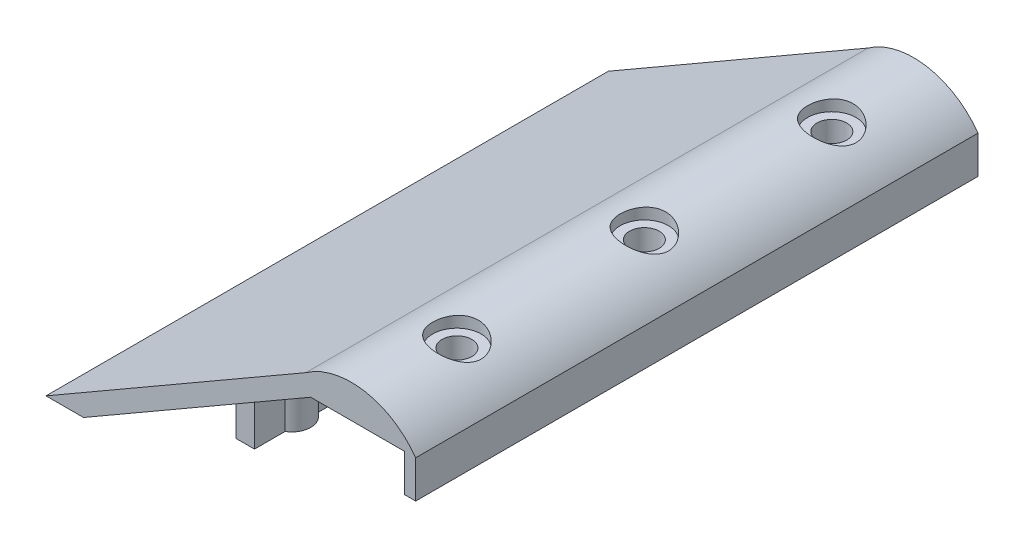
SolidWorks part; units mm, degrees
ref_plane "Alzado" through (0, 0, 0) normal (0, 0, 1) x (1, 0, 0)
ref_plane "Planta" through (0, 0, 0) normal (0, 1, 0) x (1, 0, 0)
ref_plane "Vista lateral" through (0, 0, 0) normal (1, 0, 0) x (0, 0, -1)
sketch "Croquis1" plane through (0, 0, 0) normal (0, 0, 1) x (1, 0, 0)
  line L0 (0, 34.3848) -> (0, -4.3701) construction
  line L1 (-35.1904, 0) -> (25, 0) construction
  line L2 (0, 0) -> (25, 0)
  line L3 (25, 0) -> (25, 5) construction
  line L4 (25, 5) -> (-1.3397, 5) construction
  line L5 (-1.3397, 5) -> (-70.6218, -35)
  line L6 (-70.6218, -35) -> (-60.6218, -35)
  line L7 (-60.6218, -35) -> (0, 0)
  line L8 (-73.772, -35) -> (41.2109, -35) construction
  line L9 (34.3149, -26) -> (-26.4016, -26) construction
  line L10 (-77.6138, -56) -> (49.339, -56) construction
  line L11 (0, 0) -> (25, 0) construction
  line L12 (0, 0) -> (25, 0)
  line L13 (0, 0) -> (25, 0)
  line L14 (25, 0) -> (25, -10)
  line L15 (25, -10) -> (28, -10)
  line L16 (28, -10) -> (28, 0)
  line L17 (-4.6669, 0) -> (44.3879, 0) construction
  arc A0 (-1.3397, 5) -> (28, 0) centre (10.8301, -12.1699) cw
  dimension "D8" = 10
  dimension "D10" = 21.0454
  dimension "D1" = 25
  dimension "D2" = 30
  dimension "D3" = 5
  dimension "D4" = 5
  dimension "D5" = 26
  dimension "D6" = 30
  dimension "D7" = 35
  dimension "D9" = 3
extrude "Saliente-Extruir1" add sketch "Croquis1" along normal mid plane 150 contours A0 L5 L6 L7 L2 L14 L15 L16 region at (-30.8506, -16.5652, 0)
ref_plane "Plano Tangente Para Perforacion" through (0, 8.8756, 0) normal (0, 1, 0) x (1, 0, 0)
ref_plane "Bases Soporte" through (0, -15, 0) normal (0, 1, 0) x (1, 0, 0)
sketch "Croquis2" plane through (0, -15, 0) normal (0, 1, 0) x (1, 0, 0)
  line L0 (122.6306, 0) -> (-182.6306, 0) construction
  line L1 (0, 52.1261) -> (0, -47.2849) construction
  line L2 (-30, 99.6856) -> (-30, -100.7612) construction
  line L3 (-32.5, 4.3301) -> (-32.5, 12.5)
  line L4 (-32.5, -12.5) -> (-27.5, -12.5)
  line L5 (-32.5, -12.5) -> (-32.5, -4.3301)
  line L6 (-32.5, 12.5) -> (-27.5, 12.5)
  line L7 (-27.5, -12.5) -> (-27.5, -4.3301)
  line L8 (-32.5, -12.5) -> (-27.5, 12.5) construction
  line L9 (-32.5, 12.5) -> (-27.5, -12.5) construction
  line L10 (-27.5, 4.3301) -> (-27.5, 12.5)
  line L17 (-32.5, 54.3301) -> (-32.5, 62.5)
  line L24 (-32.5, 37.5) -> (-27.5, 37.5)
  line L25 (-32.5, 37.5) -> (-32.5, 45.6699)
  line L26 (-32.5, 62.5) -> (-27.5, 62.5)
  line L27 (-27.5, 37.5) -> (-27.5, 45.6699)
  line L28 (-27.5, 54.3301) -> (-27.5, 62.5)
  line L29 (-32.5, 37.5) -> (-27.5, 62.5) construction
  line L30 (-32.5, 62.5) -> (-27.5, 37.5) construction
  line L31 (-32.5, 4.3301) -> (-32.5, 54.3301) construction
  line L32 (-32.5, -45.6699) -> (-32.5, -37.5)
  line L33 (-32.5, -62.5) -> (-27.5, -62.5)
  line L34 (-32.5, -62.5) -> (-32.5, -54.3301)
  line L35 (-32.5, -37.5) -> (-27.5, -37.5)
  line L36 (-27.5, -62.5) -> (-27.5, -54.3301)
  line L37 (-27.5, -45.6699) -> (-27.5, -37.5)
  line L38 (-32.5, -62.5) -> (-27.5, -37.5) construction
  line L39 (-32.5, -37.5) -> (-27.5, -62.5) construction
  line L40 (-32.5, 4.3301) -> (-32.5, -45.6699) construction
  arc A0 (-32.5, 4.3301) -> (-32.5, -4.3301) centre (-30, 0) ccw
  arc A2 (-27.5, -4.3301) -> (-27.5, 4.3301) centre (-30, 0) ccw
  arc A6 (-32.5, 54.3301) -> (-32.5, 45.6699) centre (-30, 50) ccw
  arc A7 (-27.5, 45.6699) -> (-27.5, 54.3301) centre (-30, 50) ccw
  arc A8 (-32.5, -45.6699) -> (-32.5, -54.3301) centre (-30, -50) ccw
  arc A9 (-27.5, -54.3301) -> (-27.5, -45.6699) centre (-30, -50) ccw
  dimension "D1" = 10
  dimension "D2" = 30
  dimension "D3" = 5
  dimension "D4" = 25
  dimension "D5" = 2
  dimension "D6" = 50
  dimension "D8" = 50
  dimension "D7" = 2
extrude "Saliente-Extruir2" add sketch "Croquis2" against normal blind 17
sketch "Croquis3" plane through (0, 8.8756, 0) normal (0, 1, 0) x (1, 0, 0)
  line L0 (0, -113.8566) -> (0, 103.3108) construction
  line L1 (55.4509, 0) -> (-87.9325, 0) construction
  line L2 (14, 0) -> (14, 50) construction
  line L3 (14, 0) -> (14, -50) construction
  line L6 (28, 75) -> (-1.3397, 75)
  line L7 (-1.3397, 75) -> (-1.3397, -75)
  line L8 (-1.3397, -75) -> (28, -75)
  line L9 (28, -75) -> (28, 75)
  line L10 (28, 75) -> (-1.3397, 75)
  line L11 (-1.3397, 75) -> (-1.3397, -75)
  line L12 (-1.3397, -75) -> (28, -75)
  line L13 (28, -75) -> (28, 75)
  circle A0 centre (14, 0) radius 3.9687
  circle A1 centre (14, 50) radius 3.9688
  circle A2 centre (14, -50) radius 3.9687
  dimension "D3" = 7.9375
  dimension "D2" = 14
  dimension "D5" = 50
  dimension "D7" = 50
  dimension "D1" = 0
  dimension "D4" = 2
  dimension "D6" = 2
extrude "Cortar-Extruir1" cut sketch "Croquis3" against normal blind 10 contours A2 | A0 | A1 region at (14, 8.8756, 0) region at (14, 8.8756, -50) region at (14, 8.8756, 50)
sketch "Croquis4" plane through (0, 8.8756, 0) normal (0, 1, 0) x (1, 0, 0)
  circle A0 centre (14, 50) radius 3.9688 construction
  circle A1 centre (14, -50) radius 3.9688 construction
  circle A2 centre (14, 0) radius 3.9687 construction
  circle A3 centre (14, 50) radius 3.9688
  circle A4 centre (14, -50) radius 3.9688
  circle A5 centre (14, 0) radius 3.9687
  circle A6 centre (14, 50) radius 6.4688
  circle A7 centre (14, 0) radius 6.4688
  circle A8 centre (14, -50) radius 6.4688
  dimension "D1" = 2.5
extrude "Cortar-Extruir2" cut sketch "Croquis4" against normal blind 3
